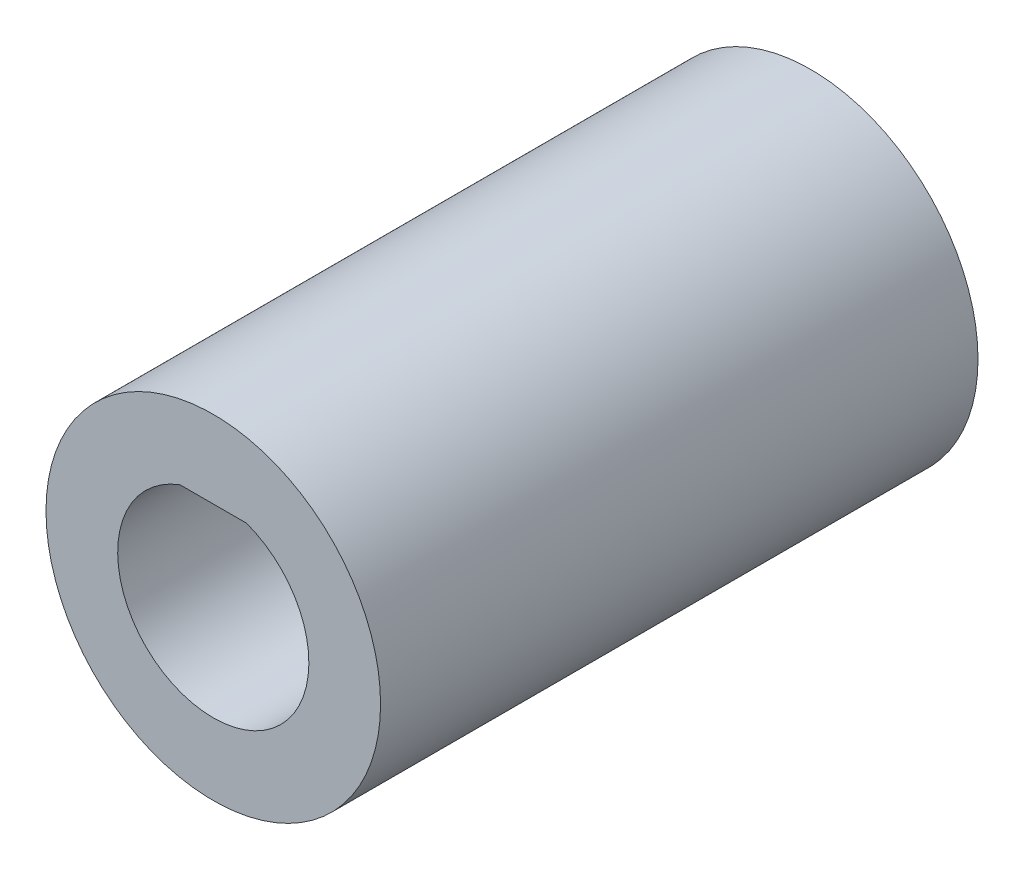
SolidWorks part; units mm, degrees
material "1060 Alloy"
ref_plane "Front Plane" through (0, 0, 0) normal (1, 0, 0) x (0, 1, 0)
ref_plane "Top Plane" through (0, 0, 0) normal (0, 0, 1) x (0, 1, 0)
ref_plane "Right Plane" through (0, 0, 0) normal (0, 1, 0) x (-1, 0, 0)
sketch "Sketch1" plane through (0, 0, 0) normal (0, 0, 1) x (0, 1, 0)
  circle A0 centre (0, 0) radius 7
  circle A1 centre (0, 0) radius 3
  dimension "D1" = 6
  dimension "D2" = 14
extrude "Boss-Extrude1" add sketch "Sketch1" along normal blind 25
sketch "Sketch2" plane through (0, 0, 25) normal (0, 0, 1) x (1, 0, 0)
  circle A0 centre (0, 0) radius 4
  circle A1 centre (0, 0) radius 3 construction
  circle A2 centre (0, 0) radius 3
  dimension "D1" = 8
extrude "Cut-Extrude1" cut sketch "Sketch2" against normal blind 13
sketch "Sketch3" plane through (0, 0, 25) normal (0, 0, 1) x (1, 0, 0)
  line L1 (1.3919, 4.25) -> (-1.3919, 4.25)
  line L2 (1.3919, 4.25) -> (1.3919, 3.75)
  line L3 (1.3919, 3.75) -> (-1.3919, 3.75)
  line L4 (-1.3919, 4.25) -> (-1.3919, 3.75)
  line L5 (1.3919, 4.25) -> (-1.3919, 3.75) construction
  line L6 (1.3919, 3.75) -> (-1.3919, 4.25) construction
  circle A0 centre (0, 0) radius 4 construction
  circle A1 centre (0, 0) radius 4 construction
  circle A2 centre (0, 0) radius 4
  point P0 (0, 4)
  circle M5 centre (0, 0) radius 4
  dimension "D1" = 0.5
extrude "Boss-Extrude2" add sketch "Sketch3" against normal up to surface (13 mm away) contours L3 M5 region at (0, 3.8503, 25) up to face at (3, 0, 12)
